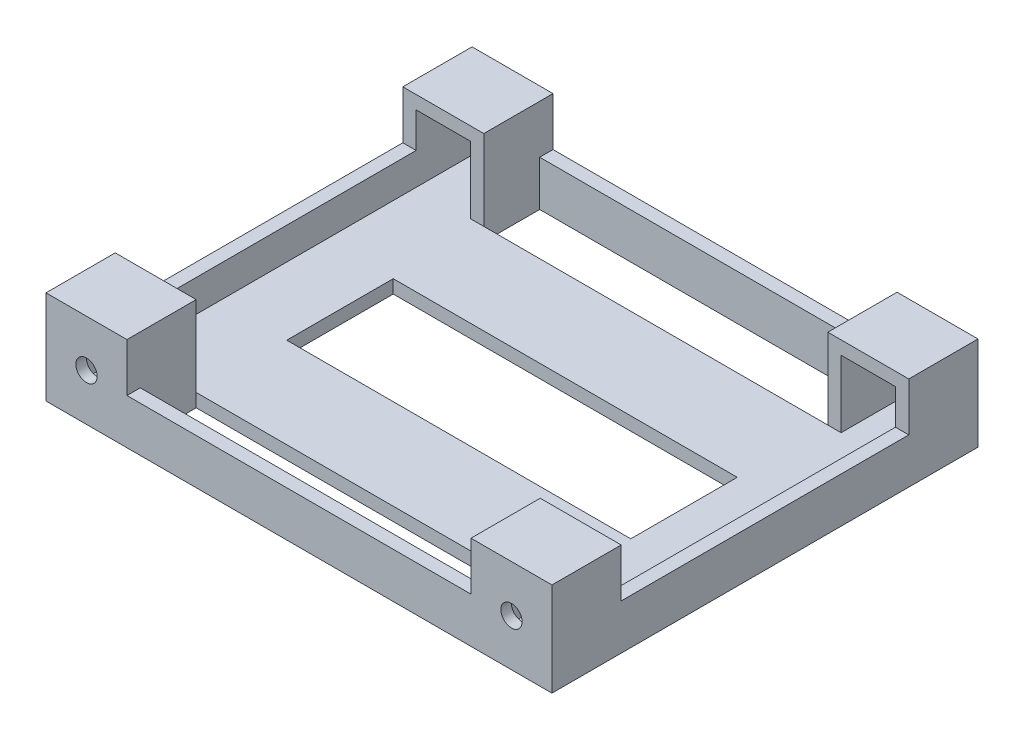
SolidWorks part; units mm, degrees
ref_plane "Front Plane" through (0, 0, 0) normal (0, 0, 1) x (1, 0, 0)
ref_plane "Top Plane" through (0, 0, 0) normal (0, 1, 0) x (1, 0, 0)
ref_plane "Right Plane" through (0, 0, 0) normal (1, 0, 0) x (0, 0, -1)
sketch "Sketch1" plane through (0, 0, 0) normal (0, 1, 0) x (1, 0, 0)
  line L1 (-45, 40) -> (45, 40)
  line L2 (-45, 40) -> (-45, -40)
  line L3 (-45, -40) -> (45, -40)
  line L4 (45, 40) -> (45, -40)
  line L5 (-45, 40) -> (45, -40) construction
  line L6 (-45, -40) -> (45, 40) construction
  point P0 (0, 0)
  dimension "D1" = 90
  dimension "D2" = 80
extrude "Boss-Extrude1" add sketch "Sketch1" along normal blind 2.5
sketch "Sketch2" plane through (0, 0, 40) normal (0, 0, 1) x (1, 0, 0)
  line L0 (-34.8, 15.1) -> (-34.8, 2.5)
  line L1 (-34.8, 15.1) -> (-45, 15.1)
  line L2 (-34.8, 2.5) -> (-45, 2.5)
  line L3 (-45, 15.1) -> (-45, 2.5)
  line L4 (-34.8, 15.1) -> (-45, 2.5) construction
  line L5 (-34.8, 2.5) -> (-45, 15.1) construction
  line L6 (-47.5, 17.6) -> (-47.5, 0)
  line L7 (-32.3, 0) -> (-47.5, 0)
  line L8 (-32.3, 17.6) -> (-32.3, 0)
  line L9 (-32.3, 17.6) -> (-47.5, 17.6)
  circle A0 centre (-39.9, 8.8) radius 2
  point P1 (-39.9, 8.8)
  point P11 (0, 0)
  line M11 (45, 2.5) -> (-45, 2.5)
  line M12 (-45, 2.5) -> (-45, 0)
  dimension "D4" = 4
  dimension "D1" = 12.6
  dimension "D2" = 10.2
  dimension "D3" = 2.5
extrude "Boss-Extrude2" add sketch "Sketch2" against normal blind 13 contours L8 L9 L6 L7 L3 L1 L0 M12 M11 region at (-39.9, 15.3326, 40)
extrude "Boss-Extrude3" add sketch "Sketch2<3>" against normal blind 2 contours L1 L3 L0 A0 M11 region at (-34.9621, 8.8, 40)
sketch "Sketch2<3>" plane through (0, 0, 40) normal (0, 0, 1) x (1, 0, 0) same geometry as "Sketch2"
mirror "Mirror1" about plane through (0, 0, 0) normal (0, 0, 1) of "Boss-Extrude2", "Boss-Extrude3" second plane through (0, 0, 0) second plane normal (1, 0, 0)
sketch "Sketch4" plane through (0, 2.5, 0) normal (0, 1, 0) x (1, 0, 0)
  line L0 (32.3, 27) -> (32.3, 40) construction
  line L1 (-32.3, 27) -> (-32.3, 40) construction
  line L2 (32.3, 40) -> (-32.3, 40) construction
  line L3 (32.3, -27) -> (32.3, -40) construction
  line L4 (-32.3, -27) -> (-32.3, -40) construction
  line L5 (-32.3, -40) -> (32.3, -40) construction
  line L6 (32.3, 37.5) -> (32.3, 40)
  line L7 (-32.3, 37.5) -> (-32.3, 40)
  line L8 (32.3, 40) -> (-32.3, 40)
  line L9 (32.3, -37.5) -> (32.3, -40)
  line L10 (-32.3, -37.5) -> (-32.3, -40)
  line L11 (-32.3, -40) -> (32.3, -40)
  line L12 (-32.3, -27) -> (-32.3, -40) construction
  line L13 (29.8, 37.5) -> (-29.8, 37.5)
  line L14 (32.3, 27) -> (32.3, 40) construction
  line L15 (32.3, -27) -> (32.3, -40) construction
  line L16 (-29.8, -37.5) -> (29.8, -37.5)
  line L17 (45, -27) -> (45, 27) construction
  line L18 (-29.8, -37.5) -> (-32.3, -37.5)
  line L19 (29.8, -37.5) -> (32.3, -37.5)
  line L20 (-29.8, 37.5) -> (-32.3, 37.5)
  line L21 (29.8, 37.5) -> (32.3, 37.5)
  line L22 (-32.3, 27) -> (-32.3, 40) construction
  line L23 (-29.8, 27) -> (-29.8, 37.5) construction
  line L24 (29.8, 27) -> (29.8, 37.5) construction
  line L25 (-29.8, -27) -> (-29.8, -37.5) construction
  line L26 (29.8, -27) -> (29.8, -37.5) construction
  line L27 (-45, 27) -> (-45, -27) construction
  line L28 (45, -27) -> (45, 27)
  line L29 (-45, 27) -> (-45, -27)
  line L30 (-47.5, 27) -> (-47.5, -27)
  line L31 (47.5, -27) -> (47.5, 27)
  line L32 (-47.5, 27) -> (-45, 27)
  line L33 (-47.5, -27) -> (-45, -27)
  line L34 (45, 27) -> (47.5, 27)
  line L35 (47.5, -27) -> (45, -27)
  dimension "D1" = 2.5
  dimension "D2" = 2.5
extrude "Boss-Extrude4" add sketch "Sketch4" along normal blind 6 and the other way blind 2.5
sketch "Sketch5" plane through (0, 2.5, 0) normal (0, 1, 0) x (1, 0, 0)
  line L0 (-32.3, -27) -> (-32.3, -40) construction
  line L1 (32.3, -37.5) -> (-32.3, -37.5) construction
  line L2 (32.3, -27) -> (32.3, -37.5) construction
  line L3 (32.3, 27) -> (32.3, 37.5) construction
  line L4 (-32.3, 37.5) -> (32.3, 37.5) construction
  line L5 (-32.3, 27) -> (-32.3, 37.5) construction
  line L6 (-32.3, -27) -> (-32.3, -37.5)
  line L7 (32.3, -37.5) -> (-32.3, -37.5)
  line L8 (32.3, -27) -> (32.3, -37.5)
  line L9 (32.3, 27) -> (32.3, 37.5)
  line L10 (-32.3, 37.5) -> (32.3, 37.5)
  line L11 (-32.3, 27) -> (-32.3, 37.5)
  line L12 (-32.3, 27) -> (32.3, 27)
  line L13 (-32.3, -27) -> (32.3, -27)
  line L15 (-32.3, 10) -> (32.3, 10)
  line L16 (-32.3, 10) -> (-32.3, -10)
  line L17 (-32.3, -10) -> (32.3, -10)
  line L18 (32.3, 10) -> (32.3, -10)
  line L19 (-32.3, 10) -> (32.3, -10) construction
  line L20 (-32.3, -10) -> (32.3, 10) construction
  point P5 (0, 0)
  dimension "D1" = 20
extrude "Cut-Extrude1" cut sketch "Sketch5" against normal through all
